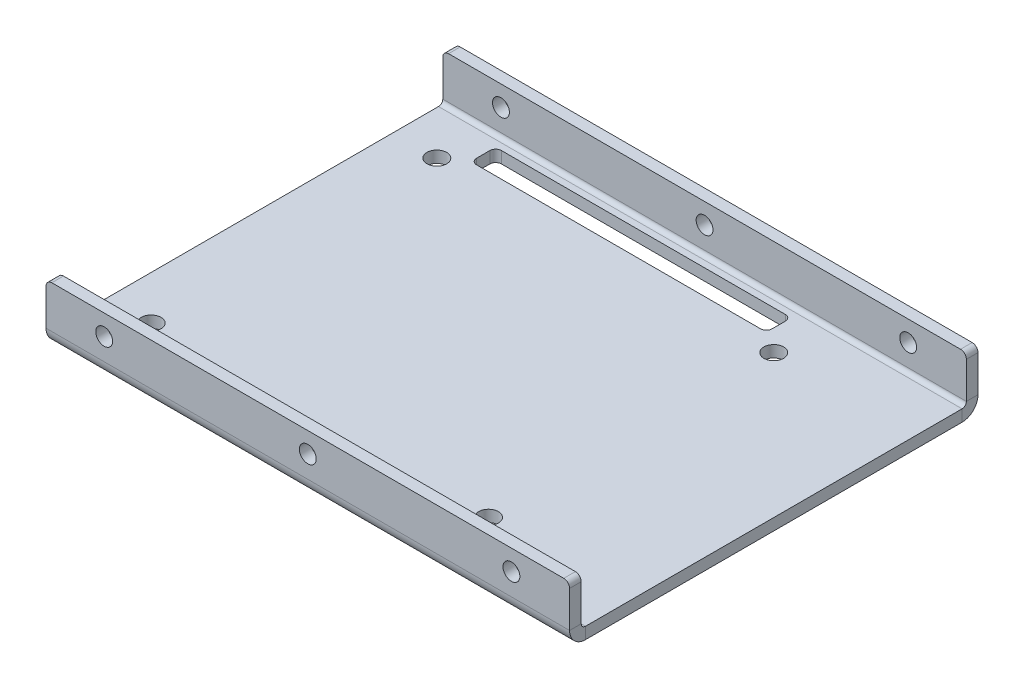
SolidWorks part; units mm, degrees
note: The reader was unsure of these and kept them because the rebuilt part matched: flange length of "边线-法兰1".
material "PE(聚乙烯)"
ref_plane "前视基准面" through (0, 0, 0) normal (0, 0, 1) x (1, 0, 0)
ref_plane "上视基准面" through (0, 0, 0) normal (0, 1, 0) x (1, 0, 0)
ref_plane "右视基准面" through (0, 0, 0) normal (1, 0, 0) x (0, 0, -1)
other "Configuration Table"
sketch "草图1" plane through (0, 0, 0) normal (0, 1, 0) x (1, 0, 0)
  line L1 (-45, 35.1) -> (45, 35.1)
  line L2 (-45, 35.1) -> (-45, -35.1)
  line L3 (-45, -35.1) -> (45, -35.1)
  line L4 (45, 35.1) -> (45, -35.1)
  line L5 (-45, 35.1) -> (45, -35.1) construction
  line L6 (-45, -35.1) -> (45, 35.1) construction
  point P0 (0, 0)
  dimension "D1" = 70.2
  dimension "D2" = 90
base flange "基体-法兰1" sketch "草图1" thickness 2 reverse thickness direction no parameters "D1"=0.7366
edge flange "边线-法兰1" sketch "草图10" flange profiles "草图10", "草图11" flange angle 90 flange length 10 flange position material inside bend radius 0.7366 thickness 2 relief rectangular parameters "D6"=10, "D8"=1
sketch "草图10" plane through (0, 0, 35.1) normal (0, 0, 1) x (1, 0, 0)
  line L0 (-45, 0) -> (45, 0) construction
  line L1 (-45, 0) -> (45, 0)
  line L2 (-45, 0) -> (-45, 8)
  line L3 (-45, 8) -> (45, 8)
  line L4 (45, 8) -> (45, 0)
sketch "草图11" plane through (0, 0, -35.1) normal (0, 0, -1) x (-1, 0, 0)
  line L0 (-45, 0) -> (45, 0) construction
  line L1 (-45, 0) -> (45, 0)
  line L2 (-45, 0) -> (-45, 8)
  line L3 (-45, 8) -> (45, 8)
  line L4 (45, 8) -> (45, 0)
bend "边线折弯1" bend radius 0.7366 bend angle 90 parameters "D5"=1
bend "边线折弯2" bend radius 0.7366 bend angle 90 parameters "D5"=2
sketch "草图12" plane through (0, 0, 0) normal (0, 1, 0) x (1, 0, 0)
  line L0 (14.2242, 22.1752) -> (14.5242, 21.8752) construction
  line L1 (-34.0359, 26.9552) -> (16.7642, 26.9552)
  line L2 (-34.0359, 26.9552) -> (-34.0359, 31.2236)
  line L3 (-34.0359, 31.2236) -> (16.7642, 31.2236)
  line L4 (16.7642, 26.9552) -> (16.7642, 31.2236)
  line L5 (14.5242, 21.8752) -> (16.4642, 21.8752) construction
  line L6 (16.4642, 21.8752) -> (16.7642, 22.1752) construction
  line L7 (16.7642, 22.1752) -> (16.7642, 26.6552) construction
  line L8 (16.7642, 26.6552) -> (16.4642, 26.9552) construction
  line L9 (16.4642, 26.9552) -> (14.5242, 26.9552) construction
  line L10 (14.5242, 26.9552) -> (14.2242, 26.6552) construction
  line L11 (14.2242, 26.6552) -> (14.2242, 22.1752) construction
  line L12 (-45, 25.9681) -> (-45, -13.3077)
  line L13 (-44.2507, -14.057) -> (-43.7449, -14.057)
  line L14 (-43.7322, -14.0697) -> (-43.7322, -19.9762)
  line L15 (-43.7449, -19.9889) -> (-44.2507, -19.9889)
  line L16 (-45, -20.7382) -> (-45, -25.9681)
  line L17 (-42.9807, -27.9874) -> (41.9527, -27.9874)
  line L18 (43.972, -25.9681) -> (43.972, 25.9681)
  line L19 (41.9527, 27.9874) -> (-42.9807, 27.9874)
  line L20 (-45, 25.9681) -> (-45, -13.3077) construction
  line L21 (-44.2507, -14.057) -> (-43.7449, -14.057) construction
  line L22 (-43.7322, -14.0697) -> (-43.7322, -19.9762) construction
  line L23 (-43.7449, -19.9889) -> (-44.2507, -19.9889) construction
  line L24 (-45, -20.7382) -> (-45, -25.9681) construction
  line L25 (-42.9807, -27.9874) -> (41.9527, -27.9874) construction
  line L26 (43.972, -25.9681) -> (43.972, 25.9681) construction
  line L27 (41.9527, 27.9874) -> (-42.9807, 27.9874) construction
  line L28 (-34.0359, 22.1752) -> (-33.7359, 21.8752) construction
  line L29 (-33.7359, 21.8752) -> (-31.7959, 21.8752) construction
  line L30 (-31.7959, 21.8752) -> (-31.4959, 22.1752) construction
  line L31 (-31.4959, 22.1752) -> (-31.4959, 26.6552) construction
  line L32 (-31.4959, 26.6552) -> (-31.7959, 26.9552) construction
  line L33 (-31.7959, 26.9552) -> (-33.7359, 26.9552) construction
  line L34 (-33.7359, 26.9552) -> (-34.0359, 26.6552) construction
  line L35 (-34.0359, 26.6552) -> (-34.0359, 22.1752) construction
  line L36 (14.2242, 22.1752) -> (14.5242, 21.8752) construction
  line L37 (14.5242, 21.8752) -> (16.4642, 21.8752) construction
  line L38 (16.4642, 21.8752) -> (16.7642, 22.1752) construction
  line L39 (16.7642, 22.1752) -> (16.7642, 26.6552) construction
  line L40 (16.7642, 26.6552) -> (16.4642, 26.9552) construction
  line L41 (16.4642, 26.9552) -> (14.5242, 26.9552) construction
  line L42 (14.5242, 26.9552) -> (14.2242, 26.6552) construction
  line L43 (14.2242, 26.6552) -> (14.2242, 22.1752) construction
  line L44 (-34.0359, 22.1752) -> (-33.7359, 21.8752) construction
  line L45 (-33.7359, 21.8752) -> (-31.7959, 21.8752) construction
  line L46 (-31.7959, 21.8752) -> (-31.4959, 22.1752) construction
  line L47 (-31.4959, 22.1752) -> (-31.4959, 26.6552) construction
  line L48 (-31.4959, 26.6552) -> (-31.7959, 26.9552) construction
  line L49 (-31.7959, 26.9552) -> (-33.7359, 26.9552) construction
  line L50 (-33.7359, 26.9552) -> (-34.0359, 26.6552) construction
  line L51 (-34.0359, 26.6552) -> (-34.0359, 22.1752) construction
  arc A8 (-42.9807, 27.9874) -> (-45, 25.9681) centre (-42.9807, 25.9681) ccw
  arc A9 (-45, -13.3077) -> (-44.2507, -14.057) centre (-44.2507, -13.3077) ccw
  arc A10 (-43.7322, -14.0697) -> (-43.7449, -14.057) centre (-43.7449, -14.0697) ccw
  arc A11 (-43.7449, -19.9889) -> (-43.7322, -19.9762) centre (-43.7449, -19.9762) ccw
  arc A12 (-44.2507, -19.9889) -> (-45, -20.7382) centre (-44.2507, -20.7382) ccw
  arc A13 (-45, -25.9681) -> (-42.9807, -27.9874) centre (-42.9807, -25.9681) ccw
  arc A14 (41.9527, -27.9874) -> (43.972, -25.9681) centre (41.9527, -25.9681) ccw
  arc A15 (43.972, 25.9681) -> (41.9527, 27.9874) centre (41.9527, 25.9681) ccw
  arc A16 (-42.9807, 27.9874) -> (-45, 25.9681) centre (-42.9807, 25.9681) ccw construction
  arc A17 (-45, -13.3077) -> (-44.2507, -14.057) centre (-44.2507, -13.3077) ccw construction
  arc A18 (-43.7322, -14.0697) -> (-43.7449, -14.057) centre (-43.7449, -14.0697) ccw construction
  arc A19 (-43.7449, -19.9889) -> (-43.7322, -19.9762) centre (-43.7449, -19.9762) ccw construction
  arc A20 (-44.2507, -19.9889) -> (-45, -20.7382) centre (-44.2507, -20.7382) ccw construction
  arc A21 (-45, -25.9681) -> (-42.9807, -27.9874) centre (-42.9807, -25.9681) ccw construction
  arc A22 (41.9527, -27.9874) -> (43.972, -25.9681) centre (41.9527, -25.9681) ccw construction
  arc A23 (43.972, 25.9681) -> (41.9527, 27.9874) centre (41.9527, 25.9681) ccw construction
  dimension "D1" = 0
extrude "切除-拉伸1" cut sketch "草图12" against normal blind 10 normal cut yes
fillet "圆角1" radius 1 4 edges at (16.7642, -1, -26.9552) (16.7642, -1, -31.2236) (-34.0359, -1, -26.9552) (-34.0359, -1, -31.2236)
fillet "圆角2" radius 1 4 edges at (45, 8, -34.1) (45, 8, 34.1) (-45, 8, 34.1) (-45, 8, -34.1)
sketch "草图13" plane through (0, 0, 0) normal (0, 1, 0) x (1, 0, 0)
  arc A0 (22.0972, 24.5422) -> (18.7972, 24.5422) centre (20.4472, 24.5422) ccw construction
  arc A1 (18.7972, 24.5422) -> (22.0972, 24.5422) centre (20.4472, 24.5422) ccw construction
  arc A2 (-35.8149, 24.5422) -> (-39.1149, 24.5422) centre (-37.4649, 24.5422) ccw construction
  arc A3 (-39.1149, 24.5422) -> (-35.8149, 24.5422) centre (-37.4649, 24.5422) ccw construction
  arc A4 (-35.8149, -24.5651) -> (-39.1149, -24.5651) centre (-37.4649, -24.5651) ccw construction
  arc A5 (-39.1149, -24.5651) -> (-35.8149, -24.5651) centre (-37.4649, -24.5651) ccw construction
  arc A6 (22.0972, -24.4799) -> (18.7972, -24.4799) centre (20.4472, -24.4799) ccw construction
  arc A7 (18.7972, -24.4799) -> (22.0972, -24.4799) centre (20.4472, -24.4799) ccw construction
  arc A8 (22.0972, 24.5422) -> (18.7972, 24.5422) centre (20.4472, 24.5422) ccw construction
  arc A9 (18.7972, 24.5422) -> (22.0972, 24.5422) centre (20.4472, 24.5422) ccw construction
  arc A10 (-35.8149, 24.5422) -> (-39.1149, 24.5422) centre (-37.4649, 24.5422) ccw construction
  arc A11 (-39.1149, 24.5422) -> (-35.8149, 24.5422) centre (-37.4649, 24.5422) ccw construction
  arc A12 (-35.8149, -24.5651) -> (-39.1149, -24.5651) centre (-37.4649, -24.5651) ccw construction
  arc A13 (-39.1149, -24.5651) -> (-35.8149, -24.5651) centre (-37.4649, -24.5651) ccw construction
  arc A14 (22.0972, -24.4799) -> (18.7972, -24.4799) centre (20.4472, -24.4799) ccw construction
  arc A15 (18.7972, -24.4799) -> (22.0972, -24.4799) centre (20.4472, -24.4799) ccw construction
hole_wizard "M2.5 间隙孔2" positions "草图18" profile "草图19" hole size "M2.5" standard "GB" end condition through all
sketch "草图18" plane through (0, 0, 35.1) normal (0, 0, 1) x (1, 0, 0)
  line L0 (44, 8) -> (-44, 8) construction
  point P0 (0, 4.5)
  point P2 (35, 4.5)
  point P9 (-35, 4.5)
  dimension "D1" = 3.5
  dimension "D2" = 35
  dimension "D3" = 35
sketch "草图19" plane through (0, 4.5, 35.1) normal (1, 0, 0) x (0, -1, 0)
  line L0 (0, 0) -> (0, 70.2)
  line L1 (0, 70.2) -> (1.45, 70.2)
  line L2 (1.45, 70.2) -> (1.45, 0)
  line L5 (1.45, 0) -> (0, 0)
  line L11 (0, -6.35) -> (0, 107.95) construction
  dimension "通孔孔直径" = 2.9
  dimension "通孔孔深度" = 70.2
sketch "草图20" plane through (0, 0, 0) normal (0, 1, 0) x (1, 0, 0)
  arc A0 (22.0972, -24.4799) -> (18.7972, -24.4799) centre (20.4472, -24.4799) ccw construction
  arc A1 (18.7972, -24.4799) -> (22.0972, -24.4799) centre (20.4472, -24.4799) ccw construction
  arc A2 (22.0972, 24.5422) -> (18.7972, 24.5422) centre (20.4472, 24.5422) ccw construction
  arc A3 (18.7972, 24.5422) -> (22.0972, 24.5422) centre (20.4472, 24.5422) ccw construction
  arc A4 (-35.8149, 24.5422) -> (-39.1149, 24.5422) centre (-37.4649, 24.5422) ccw construction
  arc A5 (-39.1149, 24.5422) -> (-35.8149, 24.5422) centre (-37.4649, 24.5422) ccw construction
  arc A6 (-35.8149, -24.5651) -> (-39.1149, -24.5651) centre (-37.4649, -24.5651) ccw construction
  arc A7 (-39.1149, -24.5651) -> (-35.8149, -24.5651) centre (-37.4649, -24.5651) ccw construction
  arc A8 (22.0972, -24.4799) -> (18.7972, -24.4799) centre (20.4472, -24.4799) ccw
  arc A9 (18.7972, -24.4799) -> (22.0972, -24.4799) centre (20.4472, -24.4799) ccw
  arc A10 (22.0972, 24.5422) -> (18.7972, 24.5422) centre (20.4472, 24.5422) ccw
  arc A11 (18.7972, 24.5422) -> (22.0972, 24.5422) centre (20.4472, 24.5422) ccw
  arc A12 (-35.8149, 24.5422) -> (-39.1149, 24.5422) centre (-37.4649, 24.5422) ccw
  arc A13 (-39.1149, 24.5422) -> (-35.8149, 24.5422) centre (-37.4649, 24.5422) ccw
  arc A14 (-35.8149, -24.5651) -> (-39.1149, -24.5651) centre (-37.4649, -24.5651) ccw
  arc A15 (-39.1149, -24.5651) -> (-35.8149, -24.5651) centre (-37.4649, -24.5651) ccw
hole_wizard "M3 间隙孔1" positions "草图21" profile "草图22" hole size "M3" standard "GB" end condition through all
sketch "草图21" plane through (0, 0, 0) normal (0, 1, 0) x (1, 0, 0)
  point P0 (-37.4649, -24.5651)
  point P3 (-37.4649, 24.5422)
  point P6 (20.4472, 24.5422)
  point P9 (20.4472, -24.4799)
sketch "草图22" plane through (-37.4649, 0, 24.5651) normal (1, 0, 0) x (0, 0, 1)
  line L0 (0, 0) -> (0, 2)
  line L1 (0, 2) -> (1.7, 2)
  line L2 (1.7, 2) -> (1.7, 0)
  line L5 (1.7, 0) -> (0, 0)
  line L11 (0, -6.35) -> (0, 107.95) construction
  dimension "通孔孔直径" = 3.4
  dimension "通孔孔深度" = 2
sketch "折弯-线1" [suppressed] plane through (0, 0, 0) normal (0, 1, 0) x (1, 0, 0)
sketch "边界框1" [suppressed] plane through (0, 0, 0) normal (0, 1, 0) x (1, 0, 0)
sheet metal parameters "钣金6" thickness 2 parameters "D1"=0.7366
flat pattern "平板型式6" [suppressed]
sketch "折弯-线2" plane through (0, 0, 0) normal (0, 1, 0) x (1, 0, 0)
sketch "边界框2" [suppressed] plane through (0, 0, 0) normal (0, 1, 0) x (1, 0, 0)
sheet metal parameters "钣金7" thickness 2 parameters "D1"=0.7366
flat pattern "平板型式6" [suppressed]
sketch "折弯-线2" plane through (0, 0, 0) normal (0, 1, 0) x (1, 0, 0)
sketch "边界框2" [suppressed] plane through (0, 0, 0) normal (0, 1, 0) x (1, 0, 0)
bend of the flat pattern "展平-<边线折弯1>1"
bend of the flat pattern "展平-<边线折弯2>1"
sheet metal parameters "钣金8" thickness 2 parameters "D1"=0.7366
flat pattern "平板型式6" [suppressed]
sketch "折弯-线2" plane through (0, 0, 0) normal (0, 1, 0) x (1, 0, 0)
sketch "边界框2" [suppressed] plane through (0, 0, 0) normal (0, 1, 0) x (1, 0, 0)
bend of the flat pattern "展平-<边线折弯1>1"
bend of the flat pattern "展平-<边线折弯2>1"
sheet metal parameters "钣金10" thickness 2 parameters "D1"=0.7366
flat pattern "平板型式6" [suppressed]
sketch "折弯-线2" plane through (0, 0, 0) normal (0, 1, 0) x (1, 0, 0)
sketch "边界框2" [suppressed] plane through (0, 0, 0) normal (0, 1, 0) x (1, 0, 0)
bend of the flat pattern "展平-<边线折弯1>1"
bend of the flat pattern "展平-<边线折弯2>1"
sheet metal parameters "钣金11" thickness 2 parameters "D1"=0.7366
flat pattern "平板型式6"
sketch "折弯-线2" plane through (0, 0, 0) normal (0, 1, 0) x (1, 0, 0)
  line L0 (45, 33.7273) -> (-45, 33.7273) construction
  line L1 (-45, -33.7273) -> (45, -33.7273) construction
  line L2 (45, 33.7273) -> (-45, 33.7273) construction
  line L3 (-45, -33.7273) -> (45, -33.7273) construction
sketch3d "边界框2" [suppressed]
  line L0 (45, -42.3546, 0) -> (-45, -42.3546, 0) construction
  line L1 (45, 42.3546, 0) -> (-45, 42.3546, 0) construction
  line L2 (45, -42.3546, 0) -> (45, 42.3546, 0) construction
  line L3 (-45, -42.3546, 0) -> (-45, 42.3546, 0) construction
bend of the flat pattern "展平-<边线折弯1>1"
bend of the flat pattern "展平-<边线折弯2>1"
